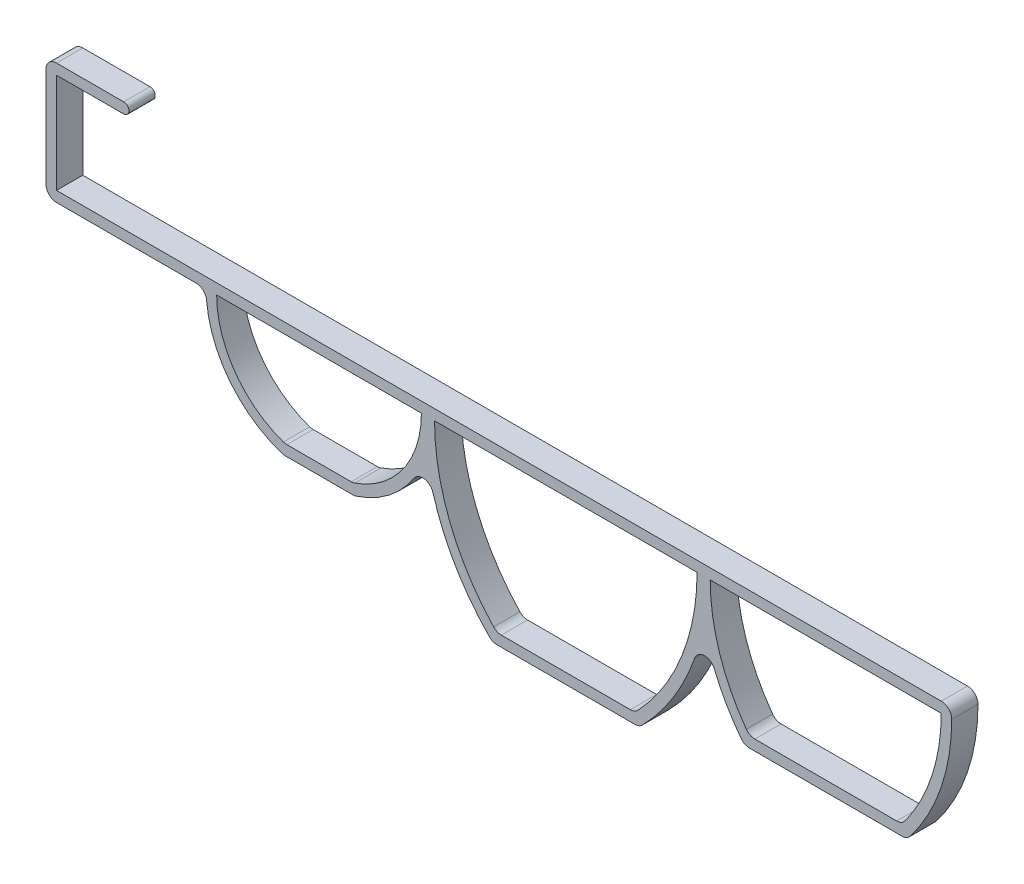
SolidWorks part; units mm, degrees
ref_plane "Front Plane" through (0, 0, 0) normal (0, 0, 1) x (1, 0, 0)
ref_plane "Top Plane" through (0, 0, 0) normal (0, 1, 0) x (1, 0, 0)
ref_plane "Right Plane" through (0, 0, 0) normal (1, 0, 0) x (0, 0, -1)
sketch "Sketch1" plane through (0, 0, 0) normal (0, 0, 1) x (1, 0, 0)
  line L0 (0, 0) -> (44, 0)
  line L1 (55, 0) -> (-55, 0) construction
  line L3 (36.5053, -22) -> (7.4947, -22)
  line L6 (0, 0) -> (-2.5, 0)
  line L7 (-2.5, 0) -> (-52.5, 0)
  line L8 (-27.5, 0) -> (-27.5, -2.8002)
  line L9 (-2.5, 0) -> (-52.5, 0)
  line L11 (-14.3582, -29) -> (-40.6418, -29)
  line L13 (-52.5, 0) -> (-55, 0)
  line L14 (-74.5, 0) -> (-74.5, -4.0886)
  line L15 (-55, 0) -> (-94, 0)
  line L17 (-68.0522, -18) -> (-80.9478, -18)
  line L19 (-67.7417, -20) -> (-81.2583, -20)
  line L20 (-53.0957, 2) -> (-95.9043, 2)
  line L21 (-1.9474, 2) -> (45.9474, 2)
  line L22 (37.4725, -24) -> (6.5275, -24)
  line L23 (-2.5, 2) -> (-52.5, 2)
  line L24 (-13.5307, -31) -> (-41.4693, -31)
  line L25 (-52.5, 2) -> (-53.0957, 2)
  line L26 (-2.5, 2) -> (-1.9474, 2)
  line L27 (-94, 0) -> (-126.5, 0)
  line L28 (-126.5, 0) -> (-126.5, 23)
  line L29 (-126.5, 23) -> (-109.6966, 23)
  line L30 (-109.6966, 23) -> (-109.6966, 21)
  line L31 (-109.6966, 21) -> (-124.5, 21)
  line L32 (-124.5, 21) -> (-124.5, 4.2956)
  line L33 (-124.5, 4.2956) -> (-124.5, 2)
  line L34 (-124.5, 2) -> (-95.9043, 2)
  arc A0 (44, 0) -> (36.5053, -22) centre (7.9633, 0) cw
  arc A1 (0, 0) -> (7.4947, -22) centre (36.0367, 0) ccw
  arc A2 (-52.5, 0) -> (-40.6418, -29) centre (-11.1102, 0) ccw
  arc A3 (-2.5, 0) -> (-14.3582, -29) centre (-43.8898, 0) cw
  arc A4 (-55, 0) -> (-68.0522, -18) centre (-73.9378, 0) cw
  arc A5 (-94, 0) -> (-80.9478, -18) centre (-75.0622, 0) ccw
  arc A6 (-53.0957, 2) -> (-67.7417, -20) centre (-73.9378, 0) cw
  arc A7 (-95.9043, 2) -> (-81.2583, -20) centre (-75.0622, 0) ccw
  arc A8 (45.9474, 2) -> (37.4725, -24) centre (7.9633, 0) cw
  arc A9 (-1.9474, 2) -> (6.5275, -24) centre (36.0367, 0) ccw
  arc A10 (-54.5, 0) -> (-41.4693, -31) centre (-11.1102, 0) ccw
  arc A11 (-0.5, 0) -> (-13.5307, -31) centre (-43.8898, 0) cw
  dimension "D1" = 44
  dimension "D2" = 2.5
  dimension "D3" = 50
  dimension "D4" = 2.5
  dimension "D5" = 39
  dimension "D6" = 2
  dimension "D8" = 32.5
  dimension "D9" = 2
  dimension "D10" = 2
  dimension "D11" = 19
  dimension "D7" = 2
extrude "Boss-Extrude1" add sketch "Sketch1" along normal blind 5 contours A7 L34 L33 L32 L31 L30 L29 L28 L27 | L20 A7 L27 L15 L13 A6 | A10 L13 A4 L17 A5 L27 A7 L19 A6 | L13 A10 A6 | A11 A9 L6 A3 L11 A2 L13 A6 A10 L24 | A9 L26 L23 L25 A6 L13 L7 L6 | A11 L6 A9 | A11 A9 L22 A8 L21 L6 L0 A0 L3 A1 region at (-1.25, 0.5459, 0) region at (-1.2401, -2.9141, 0) region at (-2.4086, -3.964, 0) region at (-27.5072, 1.0005, 0) region at (-53.8025, -2.4245, 0) region at (-59.5535, -14.568, 0) region at (-74.5, 0.9993, 0) region at (-96.3584, 1.0194, 0)
fillet "Fillet1" radius 2 20 edges at (45.9474, 2, 2.5) (7.4947, -22, 2.5) (36.5053, -22, 2.5) (37.4725, -24, 2.5) (6.5275, -24, 2.5) (-1.1998, -7.7612, 2.5) (-14.3582, -29, 2.5) (-40.6418, -29, 2.5) (-13.5307, -31, 2.5) (-41.4693, -31, 2.5) (-54.018, -6.4493, 2.5) (-68.0522, -18, 2.5) (-80.9478, -18, 2.5) (-67.7417, -20, 2.5) (-81.2583, -20, 2.5) (-96, 0, 2.5) (-109.6966, 21, 2.5) (-109.6966, 23, 2.5) (-126.5, 23, 2.5) (-126.5, 0, 2.5)
fillet "Fillet2" radius 1 1 edges at (-109.9645, 22, 2.5)
